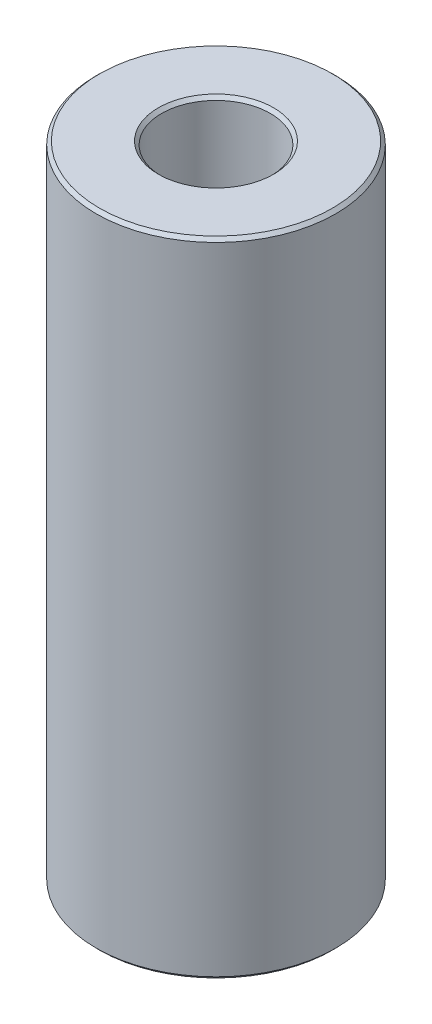
SolidWorks part; units mm, degrees
ref_plane "Front Plane" through (0, 0, 0) normal (0, 0, 1) x (1, 0, 0)
ref_plane "Top Plane" through (0, 0, 0) normal (0, 1, 0) x (1, 0, 0)
ref_plane "Right Plane" through (0, 0, 0) normal (1, 0, 0) x (0, 0, -1)
sketch "Sketch1" plane through (0, 0, 0) normal (0, 1, 0) x (1, 0, 0)
  circle A0 centre (0, 0) radius 55
  dimension "SLEEVE_OD" = 110
extrude "Boss-Extrude1" add sketch "Sketch1" along normal blind 295.0999
sketch "Sketch2" plane through (0, 0, 0) normal (0, 1, 0) x (1, 0, 0)
  circle A0 centre (0, 0) radius 24.9892
  dimension "BORE_D" = 49.9783
extrude "Cut-Extrude1" cut sketch "Sketch2" along normal through all
chamfer "Chamfer1" distance 1.4833 angle 45.61 4 edges at (0, 295.0999, 24.9892) (0, 0, 24.9892) (0, 0, 55) (0, 295.0999, 55) first distance on face at (0, 295.0999, 24.9892) first distance on face at (0, 0, 24.9892) first distance on face at (0, 295.0999, 55)
